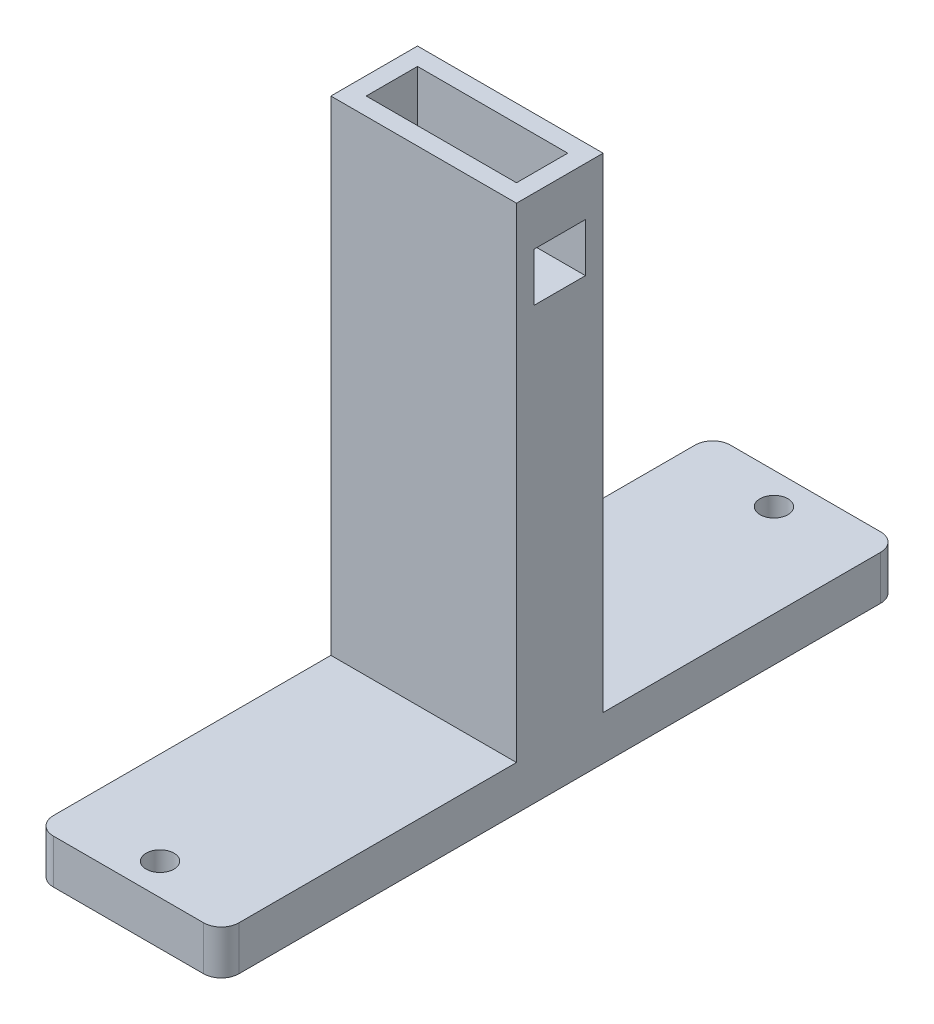
SolidWorks part; units mm, degrees
ref_plane "Front Plane" through (0, 0, 0) normal (0, 0, 1) x (1, 0, 0)
ref_plane "Top Plane" through (0, 0, 0) normal (0, 1, 0) x (1, 0, 0)
ref_plane "Right Plane" through (0, 0, 0) normal (1, 0, 0) x (0, 0, -1)
sketch "Sketch1" plane through (0, 0, 0) normal (0, 1, 0) x (1, 0, 0)
  line L0 (13.335, 6.223) -> (-13.335, 6.223)
  line L1 (10.795, -3.683) -> (-10.795, -3.683) construction
  line L2 (10.795, -3.683) -> (10.795, 3.683) construction
  line L3 (10.795, 3.683) -> (-10.795, 3.683) construction
  line L4 (-10.795, -3.683) -> (-10.795, 3.683) construction
  line L5 (10.795, -3.683) -> (-10.795, 3.683) construction
  line L6 (10.795, 3.683) -> (-10.795, -3.683) construction
  line L7 (-13.335, -6.223) -> (-13.335, 6.223)
  line L8 (13.335, -6.223) -> (-13.335, -6.223)
  line L9 (13.335, -6.223) -> (13.335, 6.223)
  line L10 (-3.2732, 0) -> (4.5518, 0) construction
  line L11 (-13.335, 6.223) -> (13.335, 6.223)
  line L12 (-13.335, 6.223) -> (-13.335, 46.101)
  line L13 (-10.795, 48.641) -> (10.795, 48.641)
  line L14 (13.335, 6.223) -> (13.335, 46.101)
  line L15 (13.335, -6.223) -> (13.335, -46.101)
  line L16 (-10.795, -48.641) -> (10.795, -48.641)
  line L17 (-13.335, -6.223) -> (-13.335, -46.101)
  arc A0 (10.795, 48.641) -> (13.335, 46.101) centre (10.795, 46.101) cw
  arc A1 (-13.335, 46.101) -> (-10.795, 48.641) centre (-10.795, 46.101) cw
  arc A2 (10.795, -48.641) -> (13.335, -46.101) centre (10.795, -46.101) ccw
  arc A3 (-13.335, -46.101) -> (-10.795, -48.641) centre (-10.795, -46.101) ccw
  circle A4 centre (0, 44.101) radius 2
  circle A5 centre (0, -44.101) radius 2
  point P0 (0, 0)
  point P20 (-13.335, 48.641)
  dimension "D5" = 2.54
  dimension "D6" = 4
  dimension "D1" = 21.59
  dimension "D2" = 7.366
  dimension "D4" = 42.418
  dimension "D7" = 4.54
  dimension "D3" = 2.54
extrude "Boss-Extrude1" add sketch "Sketch1" along normal blind 6.35 contours A1 L12 L0 L14 A0 L13 A4 | L17 A3 L16 A2 L15 L8 A5 region at (0, 0, -27.1931) region at (0, 0, 27.1931)
extrude "Boss-Extrude2" add sketch "Sketch1<3>" along normal blind 61.976 contours L8 L9 L0 L7 region at (0, 0, 0)
sketch "Sketch1<3>" plane through (0, 0, 0) normal (0, 1, 0) x (1, 0, 0) same geometry as "Sketch1"
sketch "Sketch2" plane through (0, 61.976, 0) normal (0, 1, 0) x (1, 0, 0)
  line L1 (-13.335, 6.223) -> (13.335, 6.223)
  line L2 (-13.335, 6.223) -> (-13.335, -6.223)
  line L3 (-13.335, -6.223) -> (13.335, -6.223)
  line L4 (13.335, 6.223) -> (13.335, -6.223)
  line L5 (-10.795, 3.683) -> (10.795, 3.683)
  line L6 (-10.795, 3.683) -> (-10.795, -3.683)
  line L7 (-10.795, -3.683) -> (10.795, -3.683)
  line L8 (10.795, 3.683) -> (10.795, -3.683)
extrude "Boss-Extrude3" add sketch "Sketch2" along normal blind 13.97
sketch "Sketch3" plane through (13.335, 0, 0) normal (1, 0, 0) x (0, 0, -1)
  line L0 (-6.223, 0) -> (6.223, 0) construction
  line L1 (-3.683, 68.961) -> (3.683, 68.961)
  line L2 (-3.683, 68.961) -> (-3.683, 61.976)
  line L3 (-3.683, 61.976) -> (3.683, 61.976)
  line L4 (3.683, 68.961) -> (3.683, 61.976)
  line L5 (-6.223, 75.946) -> (-6.223, 6.35) construction
  line L6 (6.223, 75.946) -> (6.223, 6.35) construction
  dimension "D1" = 61.976
  dimension "D2" = 2.54
  dimension "D3" = 2.54
  dimension "D4" = 6.985
extrude "Cut-Extrude1" cut sketch "Sketch3" against normal blind 13.97
